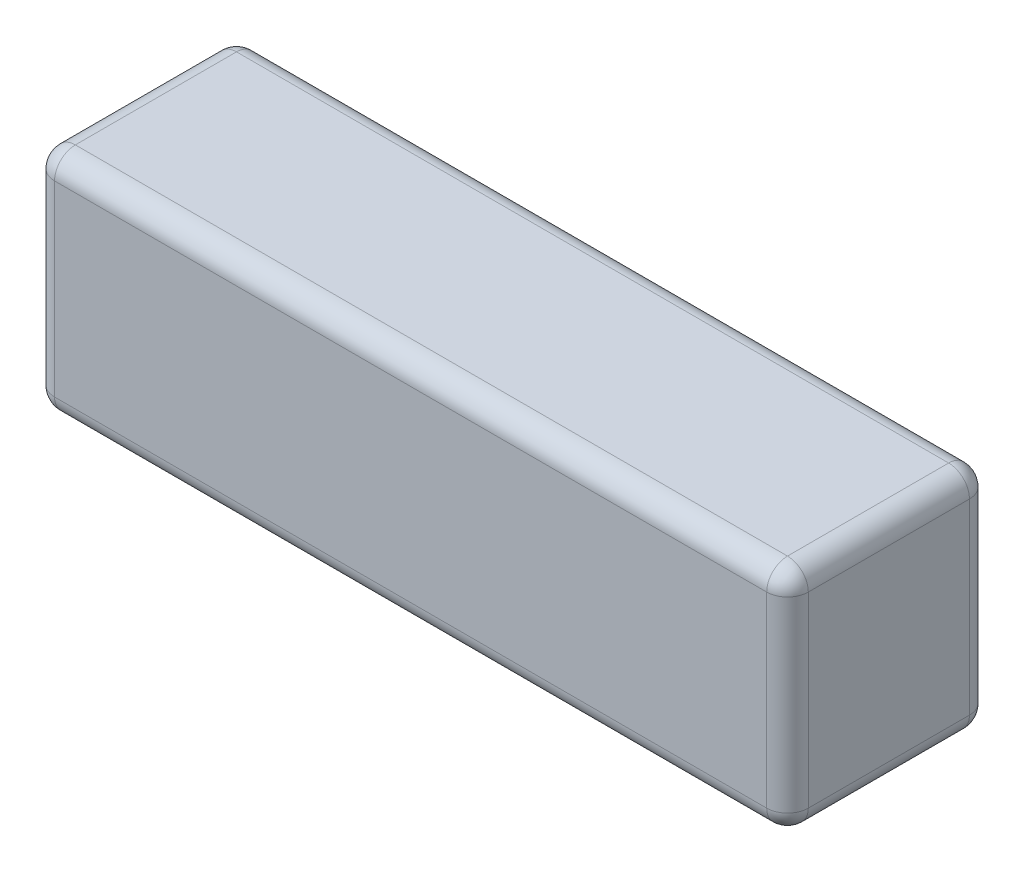
SolidWorks part; units mm, degrees
ref_plane "Front Plane" through (0, 0, 0) normal (0, 0, 1) x (1, 0, 0)
ref_plane "Top Plane" through (0, 0, 0) normal (0, 1, 0) x (1, 0, 0)
ref_plane "Right Plane" through (0, 0, 0) normal (1, 0, 0) x (0, 0, -1)
sketch "Sketch1" plane through (0, 0, 0) normal (0, 1, 0) x (1, 0, 0)
  line L1 (-72.5, -19.5) -> (72.5, -19.5)
  line L2 (-72.5, -19.5) -> (-72.5, 19.5)
  line L3 (-72.5, 19.5) -> (72.5, 19.5)
  line L4 (72.5, -19.5) -> (72.5, 19.5)
  line L5 (-72.5, -19.5) -> (72.5, 19.5) construction
  line L6 (-72.5, 19.5) -> (72.5, -19.5) construction
  point P0 (0, 0)
  dimension "D1" = 145
  dimension "D2" = 39
extrude "Boss-Extrude1" add sketch "Sketch1" along normal blind 44
fillet "Fillet1" radius 4 12 edges at (72.5, 22, 19.5) (72.5, 44, 0) (72.5, 22, -19.5) (72.5, 0, 0) (-72.5, 22, -19.5) (0, 0, -19.5) (-72.5, 0, 0) (-72.5, 22, 19.5) (0, 0, 19.5) (0, 44, 19.5) (-72.5, 44, 0) (0, 44, -19.5)
